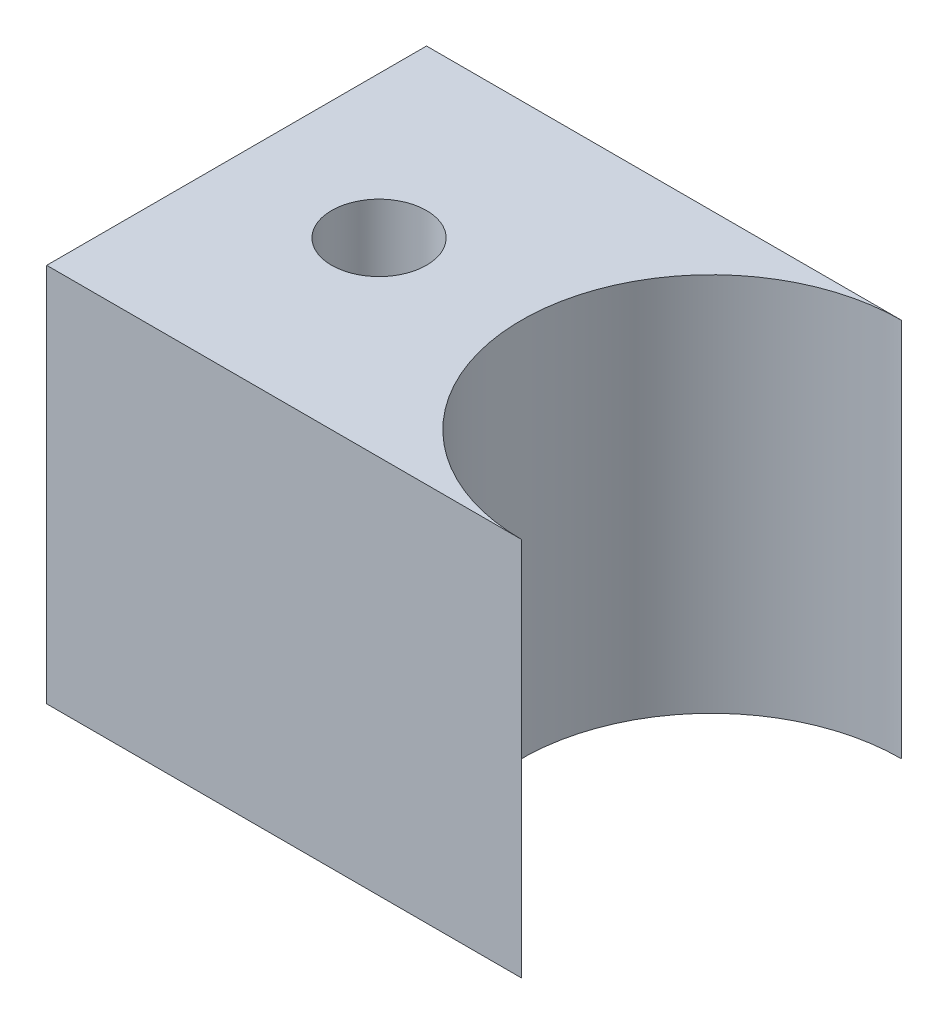
SolidWorks part; units mm, degrees
ref_plane "Front Plane" through (0, 0, 0) normal (0, 0, 1) x (1, 0, 0)
ref_plane "Top Plane" through (0, 0, 0) normal (0, 1, 0) x (1, 0, 0)
ref_plane "Right Plane" through (0, 0, 0) normal (1, 0, 0) x (0, 0, -1)
sketch "Sketch2" plane through (0, 0, 0) normal (0, 1, 0) x (1, 0, 0)
  line L1 (-15.875, -12.7) -> (15.875, -12.7)
  line L2 (-15.875, -12.7) -> (-15.875, 12.7)
  line L3 (-15.875, 12.7) -> (15.875, 12.7)
  line L4 (15.875, -12.7) -> (15.875, 12.7)
  line L5 (-15.875, -12.7) -> (15.875, 12.7) construction
  line L6 (-15.875, 12.7) -> (15.875, -12.7) construction
  circle A1 centre (15.875, 0) radius 12.7
  circle A2 centre (-6.35, 0) radius 3.175
  point P0 (0, 0)
  dimension "D3" = 6.35
  dimension "D1" = 31.75
  dimension "D2" = 25.4
  dimension "D4" = 9.525
  dimension "D5" = 12.7
extrude "Boss-Extrude2" add sketch "Sketch2" along normal blind 25.4 contours A1 L3 L2 L1 A2 region at (-15.4684, 0, 0)
sketch "Sketch3" plane through (-15.875, 0, 0) normal (-1, 0, 0) x (0, 0, 1)
  line L0 (12.7, 25.4) -> (-12.7, 25.4) construction
  circle A0 centre (0, 12.7) radius 4.7625
  dimension "D1" = 9.525
  dimension "D2" = 12.7
  dimension "D3" = 12.7
extrude "Cut-Extrude1" cut sketch "Sketch3" against normal blind 14.2875
